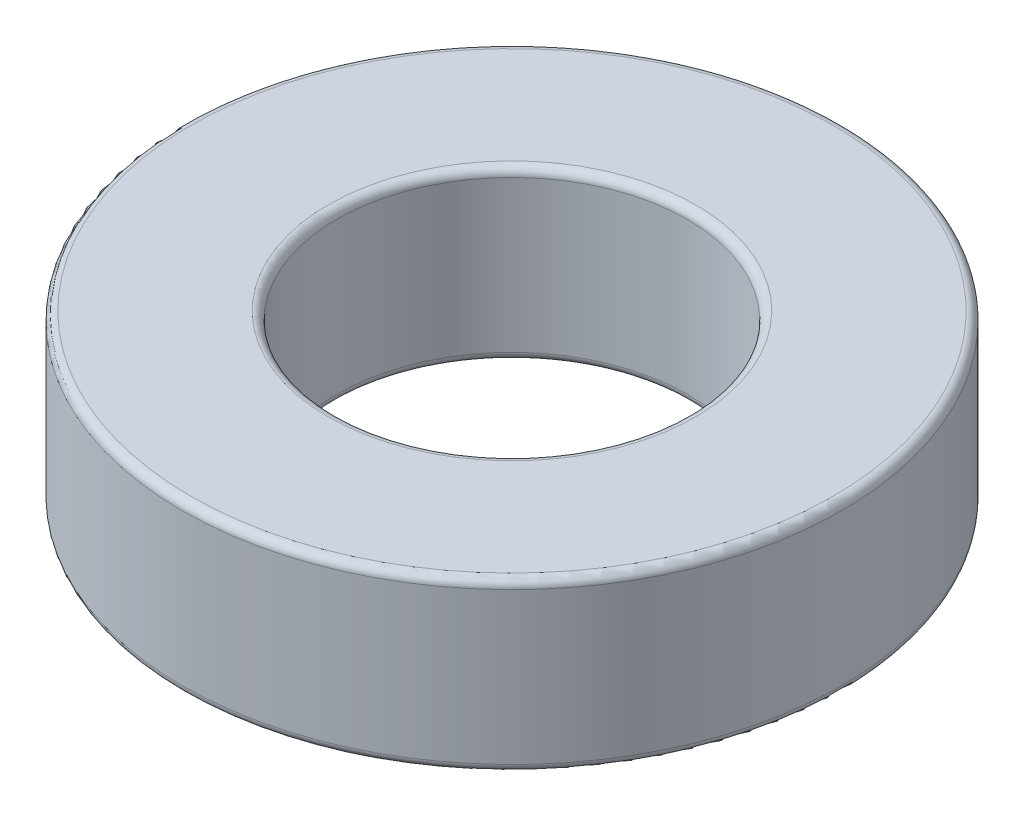
SolidWorks part; units mm, degrees
ref_plane "Front Plane" through (0, 0, 0) normal (0, 0, 1) x (1, 0, 0)
ref_plane "Top Plane" through (0, 0, 0) normal (0, 1, 0) x (1, 0, 0)
ref_plane "Right Plane" through (0, 0, 0) normal (1, 0, 0) x (0, 0, -1)
sketch "Sketch1" plane through (0, 0, 0) normal (0, 1, 0) x (1, 0, 0)
  circle A0 centre (0, 0) radius 23.5
  circle A1 centre (0, 0) radius 12.5
  dimension "D1" = 47
  dimension "D2" = 25
extrude "Boss-Extrude1" add sketch "Sketch1" along normal blind 12
fillet "Fillet1" radius 0.6 4 edges at (0, 0, 12.5) (0, 0, 23.5) (0, 12, 12.5) (0, 12, 23.5)
